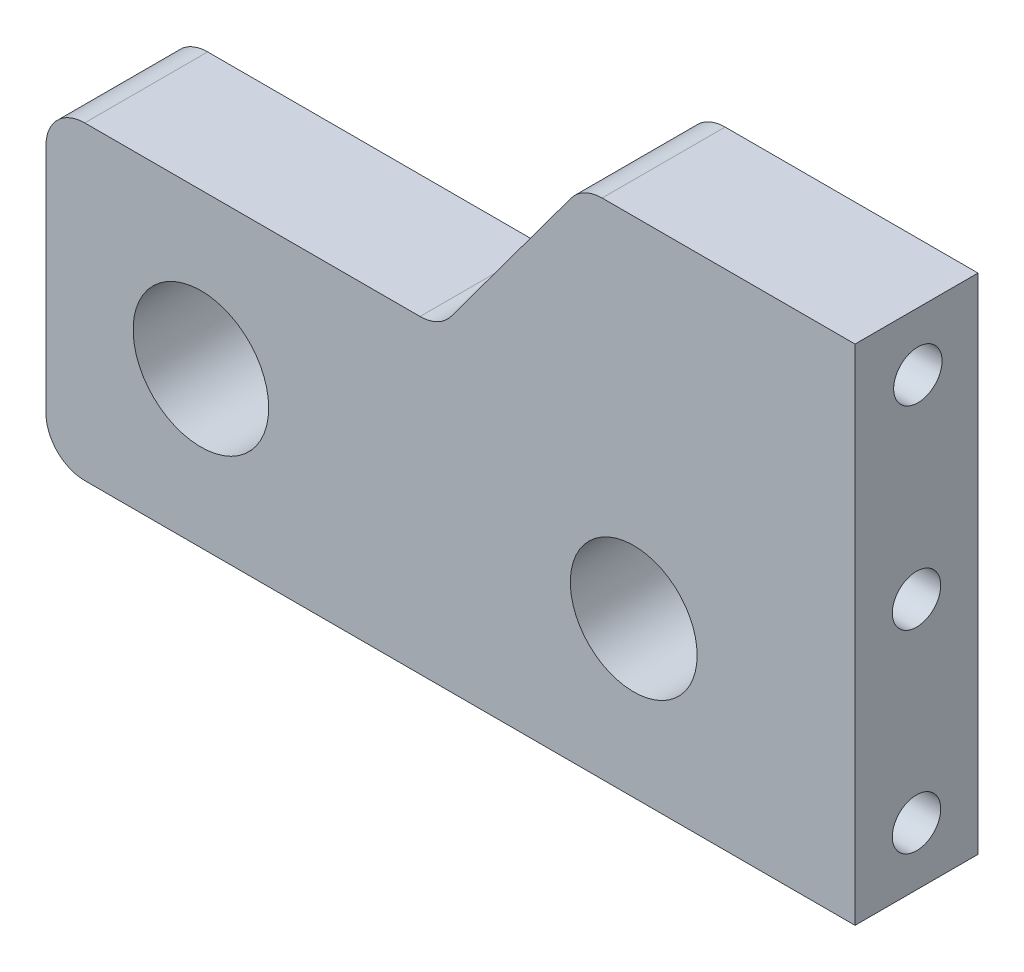
SolidWorks part; units mm, degrees
ref_plane "Front Plane" through (0, 0, 0) normal (0, 0, 1) x (1, 0, 0)
ref_plane "Top Plane" through (0, 0, 0) normal (0, 1, 0) x (1, 0, 0)
ref_plane "Right Plane" through (0, 0, 0) normal (1, 0, 0) x (0, 0, -1)
sketch "Sketch1" plane through (0, 0, 0) normal (0, 0, 1) x (1, 0, 0)
  line L0 (41.782, 8) -> (0, 8) construction
  line L1 (0, 0) -> (41.782, 0)
  line L2 (0, 0) -> (0, 16)
  line L3 (0, 16) -> (41.782, 16)
  line L4 (41.782, 0) -> (41.782, 16)
  circle A0 centre (8, 8) radius 3.5
  circle A1 centre (30.352, 8) radius 3.275
  dimension "D5" = 7
  dimension "D6" = 6.55
  dimension "D1" = 11.43
  dimension "D2" = 16
  dimension "D3" = 22.352
  dimension "D4" = 8
extrude "Boss-Extrude1" add sketch "Sketch1" along normal blind 6.35 contours L3 L4 L1 L2
extrude "Cut-Extrude1" cut sketch "Sketch1<6>" along normal blind 6.35 contours A0 L0 | L0 A0 | A1 region at (8, 6.5146, 0) region at (8, 9.4854, 0)
sketch "Sketch1<6>" plane through (0, 0, 0) normal (0, 0, 1) x (1, 0, 0) same geometry as "Sketch1"
fillet "Fillet1" radius 2 2 edges at (0, 16, 3.175) (0, 0, 3.175)
sketch "Sketch2" plane through (41.782, 0, 0) normal (1, 0, 0) x (0, 0, -1)
  line L0 (-6.35, 16) -> (0, 16) construction
  line L1 (-6.35, 0) -> (0, 0) construction
  line L4 (-6.35, 0) -> (-6.35, 16) construction
  circle A0 centre (-3.175, 13) radius 1.25
  circle A1 centre (-3.175, 3) radius 1.25
  dimension "D1" = 2.5
  dimension "D2" = 2.5
  dimension "D3" = 3
  dimension "D4" = 3
  dimension "D5" = 3.175
  dimension "D6" = 3.175
extrude "Cut-Extrude2" cut sketch "Sketch2" against normal blind 4
sketch "Sketch3" plane through (0, 0, 6.35) normal (0, 0, 1) x (1, 0, 0)
  line L0 (27.712, 26) -> (20.3263, 16)
  line L1 (41.782, 16) -> (27.712, 16)
  line L2 (41.782, 16) -> (41.782, 26)
  line L3 (41.782, 26) -> (27.712, 26)
  line L4 (27.712, 16) -> (27.712, 26)
  line L5 (2, 16) -> (41.782, 16) construction
  point P8 (0, 0)
  line M4 (41.782, 16) -> (2, 16)
  dimension "D1" = 10
extrude "Boss-Extrude2" add sketch "Sketch3" against normal blind 6.35 contours L4 L0 M4 | L4 L1 L2 L3 region at (25.2501, 19.3333, 6.35)
fillet "Fillet2" radius 2 2 edges at (20.3263, 16, 3.175) (27.712, 26, 3.175)
sketch "Sketch4" plane through (41.782, 0, 0) normal (1, 0, 0) x (0, 0, -1)
  line L0 (0, 26) -> (-6.35, 26) construction
  circle A0 centre (-3.1057, 23) radius 1.25
  dimension "D2" = 2.5
  dimension "D1" = 3
extrude "Cut-Extrude3" cut sketch "Sketch4" against normal blind 4
